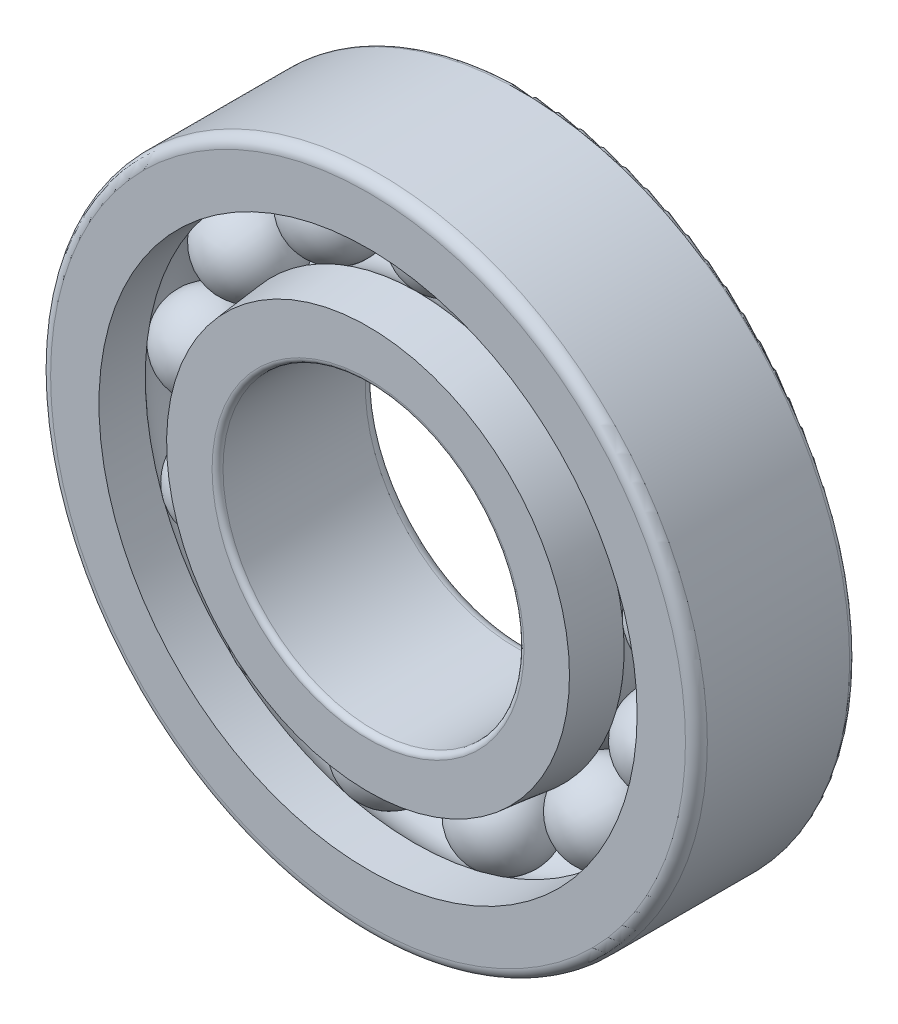
SolidWorks part; units mm, degrees
ref_plane "Front Plane" through (0, 0, 0) normal (0, 0, 1) x (1, 0, 0)
ref_plane "Top Plane" through (0, 0, 0) normal (0, 1, 0) x (1, 0, 0)
ref_plane "Right Plane" through (0, 0, 0) normal (1, 0, 0) x (0, 0, -1)
sketch "BaseSke" plane through (0, 0, 0) normal (1, 0, 0) x (0, 0, -1)
  line L0 (-47.2296, 0) -> (24.6132, 0) construction
  line L1 (-47.2296, 43.75) -> (24.6132, 43.75) construction
  line L2 (0, 129.5214) -> (0, -86.3012) construction
  line L3 (0, 51.875) -> (0, 35.625)
  line L4 (-14.5, 60) -> (14.5, 60) construction
  line L5 (-14.5, 27.5) -> (14.5, 27.5) construction
  arc A0 (0, 51.875) -> (0, 35.625) centre (0, 43.75) ccw
  dimension "Ball_diameter" = 16.25
  dimension "D1" = 43.75
revolve "Ball" add sketch "BaseSke" angle 360 about L3
sketch "OuterRaceSke" plane through (0, 0, 0) normal (1, 0, 0) x (0, 0, -1)
  line L0 (0, 0) -> (0, 87.5396) construction
  line L1 (-14.5, 60) -> (14.5, 60)
  line L2 (-14.5, 60) -> (-14.5, 49.1667)
  line L3 (-14.5, 49.1667) -> (-6.0426, 49.1667)
  line L4 (14.5, 60) -> (14.5, 50.6907)
  line L5 (-50.3916, 0) -> (55.2197, 0) construction
  line L6 (-47.2296, 43.75) -> (24.6132, 43.75) construction
  line L8 (14.5, 50.6907) -> (5.4727, 49.7419)
  line L9 (0, 49.1667) -> (-2.5325, 58.6181) construction
  line L10 (0, 49.1667) -> (5.4727, 49.7419) construction
  arc A0 (5.4727, 49.7419) -> (-6.0426, 49.1667) centre (0, 43.75) ccw
  dimension "D4" = 16.23
  dimension "D2" = 98.3333
  dimension "D3" = 6
revolve "OuterRace" add sketch "OuterRaceSke" angle 360 about L5
sketch "InnerRaceSke" plane through (0, 0, 0) normal (1, 0, 0) x (0, 0, -1)
  line L0 (-70.8626, 0) -> (113.5527, 0) construction
  line L1 (0, 58.441) -> (0, -70.8113) construction
  line L2 (-14.5, 27.5) -> (14.5, 27.5)
  line L3 (-14.5, 27.5) -> (-14.5, 38.3333)
  line L4 (-14.5, 38.3333) -> (-6.0426, 38.3333)
  line L5 (14.5, 27.5) -> (14.5, 38.3333)
  line L6 (0, 129.5214) -> (0, -86.3012) construction
  line L7 (6.0426, 38.3333) -> (14.5, 38.3333)
  arc A0 (-6.0426, 38.3333) -> (6.0426, 38.3333) centre (0, 43.75) ccw
  arc A1 (0, 51.875) -> (0, 35.625) centre (0, 43.75) ccw construction
  dimension "D2" = 16.23
  dimension "D1" = 76.6667
revolve "InnerRace" add sketch "InnerRaceSke" angle 360 about L0
fillet "Fillet1" radius 2 2 edges at (27.5, 0, -14.5) (60, 0, 14.5)
fillet "Fillet2" radius 1 2 edges at (60, 0, -14.5) (27.5, 0, 14.5)
sketch "CutInnerRaceSke" plane through (0, 0, 0) normal (1, 0, 0) x (0, 0, -1)
  line L0 (-6.0426, 38.3333) -> (-14.5, 38.3333)
  line L1 (-14.5, 38.3333) -> (-14.5, 36.8093)
  line L2 (-14.5, 36.8093) -> (-5.4727, 37.7581)
  line L3 (-5.4727, 37.7581) -> (0, 38.3333) construction
  line L4 (0, 58.441) -> (0, -70.8113) construction
  line L5 (-28.3066, 0) -> (35.2466, 0) construction
  arc A0 (-6.0426, 38.3333) -> (-5.4727, 37.7581) centre (0, 43.75) ccw
  arc A1 (-6.0426, 38.3333) -> (6.0426, 38.3333) centre (0, 43.75) ccw construction
  dimension "D1" = 6
revolve "CutInnerRace" cut sketch "CutInnerRaceSke" angle 360 about L5
pattern_circular "CirPatternBall" count 13 over 360 about axis through (0, 0, 50.3916) along (0, 0, -1) of "Ball"
sketch "SimplifiedSke" plane through (0, 0, 0) normal (1, 0, 0) x (0, 0, -1)
  line L0 (37.5911, 0) -> (-37.5911, 0) construction
  circle A0 centre (0, 43.75) radius 8.125
  arc A1 (0, 51.875) -> (0, 35.625) centre (0, 43.75) ccw construction
revolve "Simplified" [suppressed] add sketch "SimplifiedSke" angle 360 about L0
equation "\"D1@BaseSke\" =  (\"Bearing_Outside_Diameter@BaseSke\"  +  \"Bearing_Inside_Diameter@BaseSke\"  )  / 4"
equation "\"Ball_diameter@BaseSke\" =  ( \"Bearing_Outside_Diameter@BaseSke\" - \"Bearing_Inside_Diameter@BaseSke\" ) / 4 "
equation "\"D2@OuterRaceSke\" = \"Bearing_Outside_Diameter@BaseSke\" -  ( \"Bearing_Outside_Diameter@BaseSke\" - \"Bearing_Inside_Diameter@BaseSke\" )  / 3"
equation "\"D4@OuterRaceSke\" = (  \"Bearing_Outside_Diameter@BaseSke\" - \"Bearing_Inside_Diameter@BaseSke\" ) / 4 -0.02"
equation "\"D3@OuterRaceSke\" = \"Angle@OuterRaceSke\"/2.5"
equation "\"D1@InnerRaceSke\" = \"Bearing_Inside_Diameter@BaseSke\" +  ( \"Bearing_Outside_Diameter@BaseSke\" - \"Bearing_Inside_Diameter@BaseSke\" )  / 3"
equation "\"D2@InnerRaceSke\" = \"D4@OuterRaceSke\""
equation "\"D1@CirPatternBall\" = int( \"D1@BaseSke\"* pi  * 2 / \"Ball_diameter@BaseSke\"/1.2 ) -1"
equation "\"D1@CutInnerRaceSke\" = \"D3@OuterRaceSke\""
